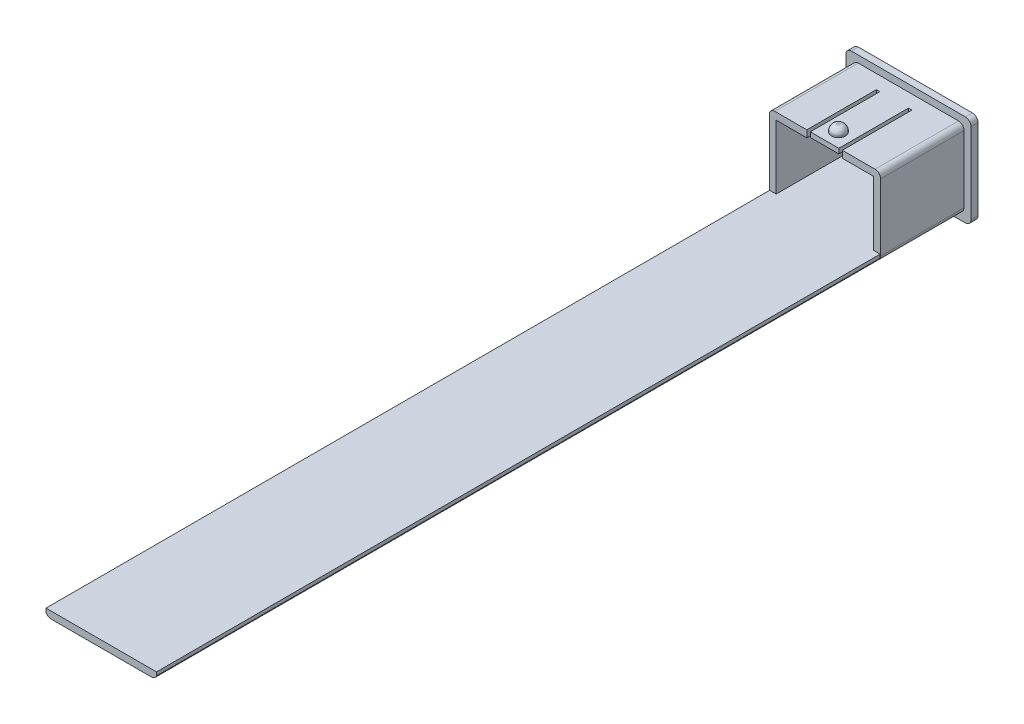
SolidWorks part; units mm, degrees
ref_plane "Front Plane" through (0, 0, 0) normal (0, 0, 1) x (1, 0, 0)
ref_plane "Top Plane" through (0, 0, 0) normal (0, 1, 0) x (1, 0, 0)
ref_plane "Right Plane" through (0, 0, 0) normal (1, 0, 0) x (0, 0, -1)
sketch "Sketch1" plane through (0, 0, 0) normal (0, 0, 1) x (1, 0, 0)
  line L1 (0, 0) -> (25.4, 0)
  line L2 (0, 0) -> (0, 17.78)
  line L3 (0, 17.78) -> (25.4, 17.78)
  line L4 (25.4, 0) -> (25.4, 17.78)
  dimension "D1" = 25.4
  dimension "D2" = 17.78
extrude "Boss-Extrude1" add sketch "Sketch1" along normal blind 19.05 contours L2 L3 L4 L1
sketch "Sketch2" plane through (0, 0, 19.05) normal (0, 0, 1) x (1, 0, 0)
  line L0 (25.4, 0) -> (25.4, 17.78) construction
  line L1 (0, 0) -> (25.4, 0)
  line L2 (0, 0) -> (0, 0.7937)
  line L3 (0, 0.7937) -> (25.4, 0.7937)
  line L4 (25.4, 0) -> (25.4, 0.7937)
  dimension "D1" = 0.7937
extrude "Boss-Extrude2" add sketch "Sketch2" along normal blind 165.1
sketch "Sketch3" plane through (0, 0, 0) normal (0, 0, -1) x (-1, 0, 0)
  line L5 (-26.9875, -1.5875) -> (1.5875, -1.5875)
  line L6 (-26.9875, -1.5875) -> (-26.9875, 19.3675)
  line L7 (-26.9875, 19.3675) -> (1.5875, 19.3675)
  line L8 (1.5875, -1.5875) -> (1.5875, 19.3675)
extrude "Boss-Extrude3" add sketch "Sketch3" along normal blind 1.5875
sketch "Sketch4" plane through (0, 0, 19.05) normal (0, 0, 1) x (1, 0, 0)
  line L1 (25.4, 0.7937) -> (0, 0.7937) construction
  line L6 (1.5875, 0.7938) -> (23.7549, 0.7938)
  line L7 (1.5875, 0.7938) -> (1.5875, 16.1925)
  line L8 (1.5875, 16.1925) -> (23.7549, 16.1925)
  line L9 (23.7549, 0.7938) -> (23.7549, 16.1925)
extrude "Cut-Extrude1" cut sketch "Sketch4" against normal blind 19.05
sketch "Sketch5" plane through (0, 0, -1.5875) normal (0, 0, -1) x (-1, 0, 0)
  line L0 (-12.7, 8.89) -> (-14.758, 8.89)
  line L3 (-12.7, 8.89) -> (-11.1125, 8.89)
  line L4 (-11.1125, 8.89) -> (-11.1125, 2.54)
  line L5 (-14.758, 8.89) -> (-22.6955, 8.89)
  line L6 (-11.1125, 2.54) -> (-3.175, 2.54)
  line L7 (-11.1125, 2.54) -> (-11.1125, 15.24)
  line L8 (-11.1125, 15.24) -> (-3.175, 15.24)
  line L9 (-3.175, 2.54) -> (-3.175, 15.24)
  line L10 (-18.7267, 8.89) -> (-18.7267, 4.5371) construction
  line L12 (-22.6955, 6.5342) -> (-14.758, 6.5342)
  line L13 (-22.6955, 6.5342) -> (-22.6955, 2.54)
  line L14 (-22.6955, 2.54) -> (-14.758, 2.54)
  line L15 (-14.758, 6.5342) -> (-14.758, 2.54)
  line L16 (-22.6955, 6.5342) -> (-14.758, 2.54) construction
  line L17 (-22.6955, 2.54) -> (-14.758, 6.5342) construction
  dimension "D1" = 7.9375
  dimension "D2" = 12.7
extrude "Cut-Extrude2" cut sketch "Sketch5" against normal blind 1.5875 contours L6 L9 L8 L7 L4 region at (7.1437, 8.89, -1.5875)
sketch "Sketch8" plane through (0, 0, -1.5875) normal (0, 0, -1) x (-1, 0, 0)
  line L0 (-11.1125, 8.89) -> (-15.0525, 8.89)
  line L1 (-11.1125, 2.54) -> (-11.1125, 15.24) construction
  line L2 (-15.0525, 8.89) -> (-22.99, 8.89)
  line L3 (-22.99, 8.89) -> (-22.99, 2.54)
  line L5 (-22.99, 2.54) -> (-15.0525, 2.54)
  line L6 (-22.99, 2.54) -> (-22.99, 7.3025)
  line L7 (-22.99, 7.3025) -> (-15.0525, 7.3025)
  line L8 (-15.0525, 2.54) -> (-15.0525, 7.3025)
  dimension "D1" = 4.7625
extrude "Cut-Extrude3" cut sketch "Sketch8" against normal blind 1.5875 contours L5 L8 L7 L3 region at (19.0212, 4.9212, -1.5875)
fillet "Fillet9" radius 1.27 1 edges at (25.4, 17.78, 9.525)
fillet "Fillet10" radius 1.27 1 edges at (0, 17.78, 9.525)
fillet "Fillet11" radius 1.27 1 edges at (25.4, 0, 92.075)
fillet "Fillet12" radius 1.27 1 edges at (0, 0, 92.075)
fillet "Fillet13" radius 1.27 1 edges at (-1.5875, -1.5875, -0.7937)
fillet "Fillet14" radius 1.27 1 edges at (-1.5875, 19.3675, -0.7937)
fillet "Fillet15" radius 1.27 1 edges at (26.9875, -1.5875, -0.7937)
fillet "Fillet16" radius 1.27 1 edges at (26.9875, 19.3675, -0.7937)
sketch "Sketch9" plane through (0, 17.78, 0) normal (0, 1, 0) x (1, 0, 0)
  line L1 (1.27, -19.05) -> (24.13, -19.05) construction
  line L4 (15.875, -19.05) -> (9.525, -19.05)
  line L5 (15.875, -19.05) -> (15.875, -3.175)
  line L8 (15.875, -3.175) -> (16.6687, -3.175)
  line L9 (15.875, -3.175) -> (15.875, -19.05)
  line L10 (15.875, -19.05) -> (16.6688, -19.05)
  line L11 (16.6687, -3.175) -> (16.6688, -19.05)
  line M3 (1.27, -19.05) -> (24.13, -19.05)
  dimension "D2" = 0.7937
extrude "Cut-Extrude5" cut sketch "Sketch9" against normal blind 1.5875 contours L11 L8 L5 M3 region at (16.2719, 17.78, 11.1125)
sketch "Sketch11" plane through (0, 17.78, 0) normal (0, 1, 0) x (1, 0, 0)
  line L0 (15.875, -3.175) -> (9.3662, -3.175)
  line L1 (1.27, -19.05) -> (15.875, -19.05) construction
  line L2 (9.3662, -3.175) -> (8.5725, -3.175)
  line L3 (9.3662, -3.175) -> (9.3662, -19.05)
  line L4 (9.3662, -19.05) -> (8.5725, -19.05)
  line L5 (8.5725, -3.175) -> (8.5725, -19.05)
  line M7 (1.27, -19.05) -> (15.875, -19.05)
  dimension "D1" = 0.7937
extrude "Cut-Extrude6" cut sketch "Sketch11" against normal blind 1.5875 contours L2 L5 L3 M7 region at (8.9694, 17.78, 11.1125)
sketch "Sketch12" plane through (0, 0, 19.05) normal (0, 0, 1) x (1, 0, 0)
  line L0 (9.3662, 16.1925) -> (9.3662, 17.78) construction
  line L1 (15.875, 16.1925) -> (9.3662, 16.1925)
  line L2 (15.875, 16.1925) -> (15.875, 16.6598)
  line L3 (15.875, 16.6598) -> (9.3662, 16.6598)
  line L4 (9.3662, 16.1925) -> (9.3662, 16.6598)
extrude "Cut-Extrude7" cut sketch "Sketch12" against normal blind 15.875
sketch "Sketch13" plane through (0, 17.78, 0) normal (0, 1, 0) x (1, 0, 0)
  line L0 (12.6206, -19.05) -> (12.6206, -15.875)
  line L1 (9.3662, -19.05) -> (15.875, -19.05) construction
  circle A0 centre (12.6206, -15.875) radius 1.5875
extrude "Boss-Extrude5" add sketch "Sketch13" along normal blind 1.5875 contours A0
fillet "Fillet22" radius 1.27 1 edges at (12.6206, 19.3675, 17.4625) type face fillet first side face at (12.6206, 19.3675, 17.4625) second side face at (12.6206, 19.3675, 17.4625)
sketch "Sketch17" plane through (0, 0.7937, 0) normal (0, 1, 0) x (1, 0, 0)
  line L1 (1.5875, 0) -> (23.7549, 0)
  line L2 (1.5875, 0) -> (1.5875, -19.05)
  line L3 (1.5875, -19.05) -> (23.7549, -19.05)
  line L4 (23.7549, 0) -> (23.7549, -19.05)
extrude "Boss-Extrude6" add sketch "Sketch17" along normal blind 0.7937
sketch "Sketch18" plane through (0, 0.7937, 0) normal (0, 1, 0) x (1, 0, 0)
  line L1 (0.0927, -184.15) -> (25.3073, -184.15)
  line L2 (0.0927, -184.15) -> (0.0927, -19.05)
  line L3 (0.0927, -19.05) -> (25.3073, -19.05)
  line L4 (25.3073, -184.15) -> (25.3073, -19.05)
extrude "Boss-Extrude7" add sketch "Sketch18" along normal blind 0.7937
